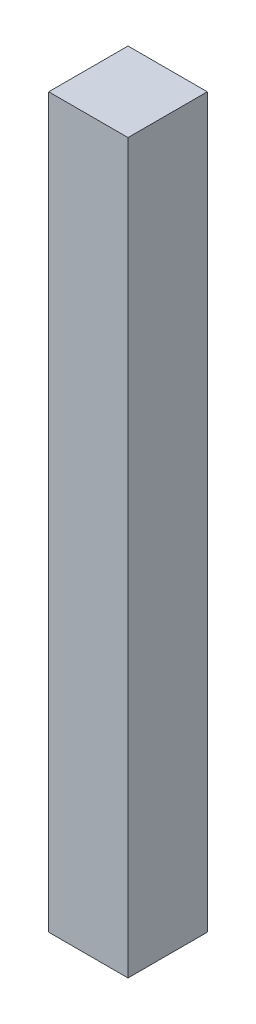
SolidWorks part; units mm, degrees
ref_plane "Front Plane" through (0, 0, 0) normal (0, 0, 1) x (1, 0, 0)
ref_plane "Top Plane" through (0, 0, 0) normal (0, 1, 0) x (1, 0, 0)
ref_plane "Right Plane" through (0, 0, 0) normal (1, 0, 0) x (0, 0, -1)
sketch "Sketch1" plane through (0, 0, 0) normal (0, 1, 0) x (1, 0, 0)
  line L1 (0, 0) -> (25.4, 0)
  line L2 (0, 0) -> (0, 25.4)
  line L3 (0, 25.4) -> (25.4, 25.4)
  line L4 (25.4, 0) -> (25.4, 25.4)
  dimension "D1" = 25.4
  dimension "D2" = 25.4
extrude "Boss-Extrude1" add sketch "Sketch1" along normal blind 609.6
sketch "Sketch3" plane through (0, 0, -25.4) normal (0, 0, -1) x (-1, 0, 0)
  line L0 (0, 609.6) -> (0, 0) construction
  line L1 (0, 466.3042) -> (-25.4, 466.3042)
  line L2 (0, 466.3042) -> (0, 609.6)
  line L3 (0, 609.6) -> (-25.4, 609.6)
  line L4 (-25.4, 466.3042) -> (-25.4, 609.6)
  line L6 (-25.4, 466.3042) -> (0, 466.3042) construction
extrude "Cut-Extrude1" cut sketch "Sketch3" against normal up to surface (25.4 mm away) up to face at (12.7, 304.8, 0)
sketch "Sketch4" [suppressed] plane through (0, 0, 0) normal (0, 0, 1) x (1, 0, 0)
  line L0 (0, 609.6) -> (0, 0) construction
  line L1 (0, 276.4933) -> (25.4, 276.4933)
  line L2 (0, 276.4933) -> (0, 609.6)
  line L3 (0, 609.6) -> (25.4, 609.6)
  line L4 (25.4, 276.4933) -> (25.4, 609.6)
  line L6 (0, 276.4933) -> (25.4, 276.4933) construction
extrude "Cut-Extrude2" [suppressed] cut sketch "Sketch4" against normal up to surface (430.6021 mm away) up to face at (12.7, 233.1521, -25.4)
sketch "Sketch5" [suppressed] plane through (0, 0, -25.4) normal (0, 0, -1) x (-1, 0, 0)
  line L0 (0, 609.6) -> (0, 0) construction
  line L1 (0, 571.9407) -> (-25.4, 571.9407)
  line L2 (0, 571.9407) -> (0, 609.6)
  line L3 (0, 609.6) -> (-25.4, 609.6)
  line L4 (-25.4, 571.9407) -> (-25.4, 609.6)
extrude "Cut-Extrude3" [suppressed] cut sketch "Sketch5" against normal up to surface (25.4 mm away) up to face at (12.7, 233.1521, 0)
sketch "Sketch6" [suppressed] plane through (0, 0, -25.4) normal (0, 0, -1) x (-1, 0, 0)
  line L0 (0, 609.6) -> (0, 0) construction
  line L1 (0, 553.696) -> (-25.4, 553.696)
  line L2 (0, 553.696) -> (0, 609.6)
  line L3 (0, 609.6) -> (-25.4, 609.6)
  line L4 (-25.4, 553.696) -> (-25.4, 609.6)
  line L6 (-25.4, 553.696) -> (0, 553.696) construction
extrude "Cut-Extrude4" [suppressed] cut sketch "Sketch6" against normal up to surface (25.4 mm away) up to face at (12.7, 233.1521, 0)
sketch "Sketch7" [suppressed] plane through (0, 0, 0) normal (0, 0, 1) x (1, 0, 0)
  line L0 (25.4, 609.6) -> (25.4, 0) construction
  line L1 (25.4, 422.1079) -> (0, 422.1079)
  line L2 (25.4, 422.1079) -> (25.4, 609.6)
  line L3 (25.4, 609.6) -> (0, 609.6)
  line L4 (0, 422.1079) -> (0, 609.6)
  line L8 (0, 422.1079) -> (25.4, 422.1079) construction
extrude "Cut-Extrude5" [suppressed] cut sketch "Sketch7" against normal up to surface (25.4 mm away) up to face at (12.7, 233.1521, -25.4)
sketch "Sketch8" [suppressed] plane through (0, 0, -25.4) normal (0, 0, -1) x (-1, 0, 0)
  line L0 (0, 609.6) -> (0, 0) construction
  line L1 (0, 319.3022) -> (-25.4, 319.3022)
  line L2 (0, 319.3022) -> (0, 609.6)
  line L3 (0, 609.6) -> (-25.4, 609.6)
  line L4 (-25.4, 319.3022) -> (-25.4, 609.6)
  line L6 (-25.4, 319.3022) -> (0, 319.3022) construction
extrude "Cut-Extrude6" [suppressed] cut sketch "Sketch8" against normal up to surface (25.4 mm away) up to face at (12.7, 233.1521, 0)
sketch "Sketch9" [suppressed] plane through (0, 0, 0) normal (0, 0, 1) x (1, 0, 0)
  line L0 (0, 609.6) -> (0, 0) construction
  line L1 (0, 329.8783) -> (25.4, 329.8783)
  line L2 (0, 329.8783) -> (0, 609.6)
  line L3 (0, 609.6) -> (25.4, 609.6)
  line L4 (25.4, 329.8783) -> (25.4, 609.6)
  line L6 (0, 329.8783) -> (25.4, 329.8783) construction
extrude "Cut-Extrude7" [suppressed] cut sketch "Sketch9" against normal up to surface (25.4 mm away) up to face at (12.7, 233.1521, -25.4)
sketch "Sketch10" [suppressed] plane through (25.4, 0, 0) normal (1, 0, 0) x (0, 0, -1)
  line L1 (25.4, 329.8783) -> (0, 329.8783)
  line L2 (25.4, 329.8783) -> (25.4, 0)
  line L3 (25.4, 0) -> (0, 0)
  line L4 (0, 329.8783) -> (0, 0)
extrude "Boss-Extrude2" [suppressed] add sketch "Sketch10" along normal blind 25.4
sketch "Sketch11" [suppressed] plane through (0, 0, -25.4) normal (0, 0, -1) x (-1, 0, 0)
  line L1 (0, 329.8783) -> (-50.8, 329.8783)
  line L2 (0, 329.8783) -> (0, 0)
  line L3 (0, 0) -> (-50.8, 0)
  line L4 (-50.8, 329.8783) -> (-50.8, 0)
extrude "Boss-Extrude3" [suppressed] add sketch "Sketch11" along normal blind 25.4
sketch "Sketch12" [suppressed] plane through (0, 0, 0) normal (0, 0, 1) x (1, 0, 0)
  line L1 (25.4, 319.3022) -> (0, 319.3022)
  line L2 (25.4, 319.3022) -> (25.4, 0)
  line L3 (25.4, 0) -> (0, 0)
  line L4 (0, 319.3022) -> (0, 0)
extrude "Boss-Extrude4" [suppressed] add sketch "Sketch12" along normal blind 25.4
sketch "Sketch13" [suppressed] plane through (25.4, 0, 0) normal (1, 0, 0) x (0, 0, -1)
  line L0 (-25.4, 0) -> (25.4, 0) construction
  line L1 (25.4, 319.3022) -> (-25.4, 319.3022)
  line L2 (25.4, 319.3022) -> (25.4, 0)
  line L3 (25.4, 0) -> (-25.4, 0)
  line L4 (-25.4, 319.3022) -> (-25.4, 0)
  line L5 (-25.4, 0) -> (-25.4, 319.3022) construction
extrude "Boss-Extrude5" [suppressed] add sketch "Sketch13" along normal blind 25.4
sketch "Sketch14" [suppressed] plane through (0, 0, -25.4) normal (0, 0, -1) x (-1, 0, 0)
  line L0 (-25.4, 422.1079) -> (-25.4, 0) construction
  line L1 (-25.4, 422.1079) -> (0, 422.1079)
  line L2 (-25.4, 422.1079) -> (-25.4, 0)
  line L3 (-25.4, 0) -> (0, 0)
  line L4 (0, 422.1079) -> (0, 0)
extrude "Boss-Extrude6" [suppressed] add sketch "Sketch14" along normal blind 25.4
sketch "Sketch15" [suppressed] plane through (25.4, 0, 0) normal (1, 0, 0) x (0, 0, -1)
  line L1 (50.8, 422.1079) -> (0, 422.1079)
  line L2 (50.8, 422.1079) -> (50.8, 0)
  line L3 (50.8, 0) -> (0, 0)
  line L4 (0, 422.1079) -> (0, 0)
extrude "Boss-Extrude7" [suppressed] add sketch "Sketch15" along normal blind 25.4
sketch "Sketch16" [suppressed] plane through (0, 0, 0) normal (0, 0, 1) x (1, 0, 0)
  line L1 (25.4, 571.9407) -> (0, 571.9407)
  line L2 (25.4, 571.9407) -> (25.4, 0)
  line L3 (25.4, 0) -> (0, 0)
  line L4 (0, 571.9407) -> (0, 0)
extrude "Boss-Extrude8" [suppressed] add sketch "Sketch16" along normal blind 25.4
sketch "Sketch17" [suppressed] plane through (25.4, 0, 0) normal (1, 0, 0) x (0, 0, -1)
  line L1 (25.4, 571.9407) -> (-25.4, 571.9407)
  line L2 (25.4, 571.9407) -> (25.4, 0)
  line L3 (25.4, 0) -> (-25.4, 0)
  line L4 (-25.4, 571.9407) -> (-25.4, 0)
extrude "Boss-Extrude9" [suppressed] add sketch "Sketch17" along normal blind 25.4
sketch "Sketch18" [suppressed] plane through (0, 0, -25.4) normal (0, 0, -1) x (-1, 0, 0)
  line L1 (0, 276.4933) -> (-25.4, 276.4933)
  line L2 (0, 276.4933) -> (0, 0)
  line L3 (0, 0) -> (-25.4, 0)
  line L4 (-25.4, 276.4933) -> (-25.4, 0)
extrude "Boss-Extrude10" [suppressed] add sketch "Sketch18" along normal blind 25.4
sketch "Sketch19" [suppressed] plane through (25.4, 0, 0) normal (1, 0, 0) x (0, 0, -1)
  line L1 (50.8, 276.4933) -> (0, 276.4933)
  line L2 (50.8, 276.4933) -> (50.8, 0)
  line L3 (50.8, 0) -> (0, 0)
  line L4 (0, 276.4933) -> (0, 0)
extrude "Boss-Extrude11" [suppressed] add sketch "Sketch19" along normal blind 25.4
sketch "Sketch22" [suppressed] plane through (25.4, 0, 0) normal (1, 0, 0) x (0, 0, -1)
  line L1 (0, 553.696) -> (25.4, 553.696)
  line L2 (0, 553.696) -> (0, 0)
  line L3 (0, 0) -> (25.4, 0)
  line L4 (25.4, 553.696) -> (25.4, 0)
extrude "Boss-Extrude14" [suppressed] add sketch "Sketch22" along normal blind 25.4
sketch "Sketch23" [suppressed] plane through (0, 0, -25.4) normal (0, 0, -1) x (-1, 0, 0)
  line L1 (-50.8, 553.696) -> (0, 553.696)
  line L2 (-50.8, 553.696) -> (-50.8, 0)
  line L3 (-50.8, 0) -> (0, 0)
  line L4 (0, 553.696) -> (0, 0)
extrude "Boss-Extrude15" [suppressed] add sketch "Sketch23" along normal blind 25.4
sketch "Sketch24" plane through (0, 0, 0) normal (0, 0, 1) x (1, 0, 0)
  line L0 (25.4, 466.3042) -> (25.4, 0) construction
  line L1 (0, 466.3042) -> (25.4, 466.3042)
  line L2 (0, 466.3042) -> (0, 0)
  line L3 (0, 0) -> (25.4, 0)
  line L4 (25.4, 466.3042) -> (25.4, 0)
  point P5 (25.4, 9.3634)
  point P10 (0, 0)
extrude "Boss-Extrude16" add sketch "Sketch24" along normal blind 25.4
sketch "Sketch25" plane through (25.4, 0, 0) normal (1, 0, 0) x (0, 0, -1)
  line L1 (-25.4, 0) -> (25.4, 0)
  line L2 (-25.4, 0) -> (-25.4, 466.3042)
  line L3 (-25.4, 466.3042) -> (25.4, 466.3042)
  line L4 (25.4, 0) -> (25.4, 466.3042)
extrude "Boss-Extrude17" add sketch "Sketch25" along normal blind 25.4
